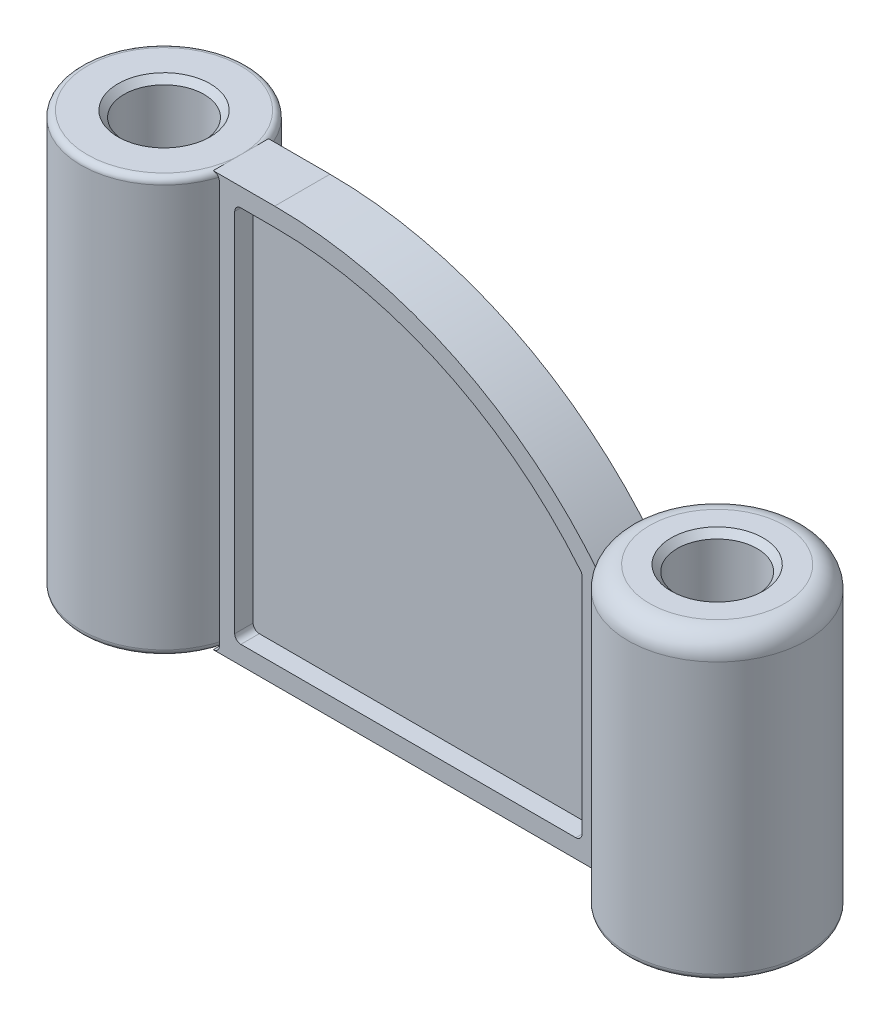
SolidWorks part; units mm, degrees
ref_plane "Спереди" through (0, 0, 0) normal (0, 0, 1) x (1, 0, 0)
ref_plane "Сверху" through (0, 0, 0) normal (0, 1, 0) x (1, 0, 0)
ref_plane "Справа" through (0, 0, 0) normal (1, 0, 0) x (0, 0, -1)
sketch "Эскиз1" plane through (0, 0, 0) normal (0, 0, 1) x (1, 0, 0)
  line L0 (-64, 0) -> (64, 0)
  line L1 (62, 2) -> (62, 90)
  line L2 (69, 97) -> (91, 97)
  line L3 (91, 97) -> (91, 0)
  line L4 (91, 0) -> (64, 0)
  line L5 (-62, 2) -> (-62, 133)
  line L6 (-64, 135) -> (-89, 135)
  line L7 (-89, 135) -> (-89, 0)
  line L8 (-89, 0) -> (-64, 0)
  line L9 (-64, 135) -> (-44, 135)
  line L10 (-44, 129) -> (-44, 0)
  line L11 (56, 80.7775) -> (56, 8)
  line L12 (54, 6) -> (-55, 6)
  line L13 (-57, 8) -> (-57, 127)
  line L14 (-44, 129) -> (-55, 129)
  line L15 (-44, 135) -> (-64, 135)
  arc A0 (62, 83.6002) -> (-44, 135) centre (-44, 0) ccw
  arc A1 (55.5433, 82.0496) -> (-44, 129) centre (-44, 0) ccw
  arc A2 (54, 6) -> (56, 8) centre (54, 8) ccw
  arc A3 (56, 80.7775) -> (55.5433, 82.0496) centre (54, 80.7775) ccw
  arc A4 (-57, 8) -> (-55, 6) centre (-55, 8) ccw
  arc A5 (-55, 129) -> (-57, 127) centre (-55, 127) ccw
  arc A6 (69, 97) -> (62, 90) centre (69, 90) ccw
  arc A7 (62, 2) -> (64, 0) centre (64, 2) ccw
  arc A8 (-64, 0) -> (-62, 2) centre (-64, 2) ccw
  arc A9 (-62, 133) -> (-64, 135) centre (-64, 133) ccw
  dimension "D5" = 270
  dimension "D8" = 2
  dimension "D12" = 2
  dimension "D13" = 2
  dimension "D9" = 2
  dimension "D11" = 7
  dimension "D17" = 2
  dimension "D18" = 2
  dimension "D19" = 2
  dimension "D1" = 135
  dimension "D2" = 180
  dimension "D3" = 97
  dimension "D4" = 135
  dimension "D6" = 6
  dimension "D7" = 6
  dimension "D10" = 25
  dimension "D14" = 35
  dimension "D15" = 32
  dimension "D16" = 29
revolve "Повернуть1" add sketch "Эскиз1" angle 360 about L7 region at (-75.5062, 67.5, 0)
revolve "Повернуть2" add sketch "Эскиз1<4>" angle 360 about L3 region at (76.5529, 48.3386, 0)
sketch "Эскиз1<4>" plane through (0, 0, 0) normal (0, 0, 1) x (1, 0, 0) same geometry as "Эскиз1"
extrude "Бобышка-Вытянуть1" add sketch "Эскиз1<5>" along normal blind 9 and the other way blind 9 separate body contours A9 L5 A8 L0 L12 A4 L13 A5 L14 A1 A3 L11 A2 A7 L1 A0 L9 region at (-62.4542, 0.4542, 0)
sketch "Эскиз1<5>" plane through (0, 0, 0) normal (0, 0, 1) x (1, 0, 0) same geometry as "Эскиз1"
extrude "Бобышка-Вытянуть2" add sketch "Эскиз1<6>" along normal blind 3 and the other way blind 3 contours L11 A3 A1 L10 L12 A2 | L14 A5 L13 A4 L12 L10 region at (-50.4935, 67.5, 0) region at (2.5328, 61.1353, 0)
sketch "Эскиз1<6>" plane through (0, 0, 0) normal (0, 0, 1) x (1, 0, 0) same geometry as "Эскиз1"
sketch3d "Трехмерный эскиз1"
  line L0 (62, 83.6002, 9) -> (62, 83.6002, -9) construction
  line L1 (-64, 135, -9) -> (-64, 135, 9) construction
  line L2 (-64, 135, 9) -> (-44, 135, 9) construction
  line L3 (-44, 135, -9) -> (-64, 135, -9) construction
  line L4 (62, 83.6002, 9) -> (62, 83.6002, -9)
  line L5 (-64, 135, -9) -> (-64, 135, 9)
  line L6 (-64, 135, 9) -> (-44, 135, 9)
  line L7 (-44, 135, -9) -> (-64, 135, -9)
  arc A0 (62, 83.6002, 9) -> (-44, 135, 9) centre (-44, 0, 9) ccw construction
  arc A1 (62, 83.6002, -9) -> (-44, 135, -9) centre (-44, 0, -9) ccw construction
  arc A2 (62, 83.6002, 9) -> (-44, 135, 9) centre (-44, 0, 9) ccw
  arc A3 (62, 83.6002, -9) -> (-44, 135, -9) centre (-44, 0, -9) ccw
  point P3 (-44, 0, 144)
  point P4 (-44, 0, 144)
  point P7 (-44, 0, 126)
  point P9 (-44, 0, 126)
sketch "Эскиз2" plane through (0, 0, 0) normal (0, 1, 0) x (1, 0, 0)
  line L0 (-89, 0) -> (91, 0) construction
  circle A0 centre (-89, 0) radius 13
  circle A1 centre (91, 0) radius 13
  dimension "D1" = 26
  dimension "D2" = 26
extrude "Вырез-Вытянуть1" cut sketch "Эскиз2" along normal up to surface (135 mm away) and the other way blind 10 contours A0 | A1 up to face at (-89, 135, 25)
chamfer "Фаска1" distance 2 angle 45 2 edges at (78, 0, 0) (104, 97, 0)
chamfer "Фаска2" distance 2 angle 45 2 edges at (-89, 0, 13) (-89, 135, -13)
equation "\"A\"= 135мм"
equation "\"B\"= 58мм"
equation "\"C\"= 180мм"
equation "\"D\"= 26мм"
equation "\"Y\"= 1.5 * \"B\" + 10мм"
equation "\"D1@Эскиз1\"=\"A\""
equation "\"D2@Эскиз1\"=\"C\""
equation "\"D3@Эскиз1\"=\"Y\""
equation "\"D4@Эскиз1\"=\"A\""
equation "\"D1@Эскиз2\"=\"D\""
equation "\"D2@Эскиз2\"=\"D\""
